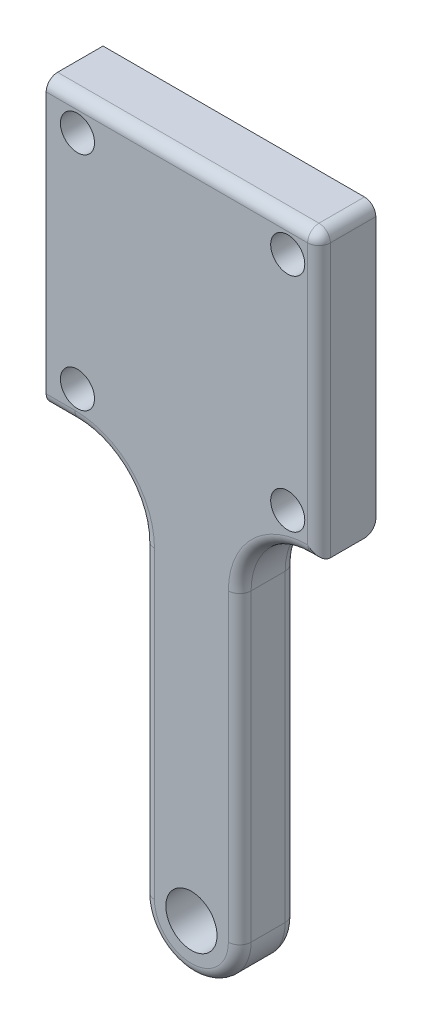
SolidWorks part; units mm, degrees
ref_plane "Alzado" through (0, 0, 0) normal (0, 0, 1) x (1, 0, 0)
ref_plane "Planta" through (0, 0, 0) normal (0, 1, 0) x (1, 0, 0)
ref_plane "Vista lateral" through (0, 0, 0) normal (1, 0, 0) x (0, 0, -1)
sketch "Croquis1" plane through (0, 0, 0) normal (0, 0, 1) x (1, 0, 0)
  line L0 (-2.2, 41.0126) -> (21, 41.0126) construction
  line L1 (21.9, 40.0126) -> (21.9, -1.4874) construction
  line L2 (-2.1, -1.4874) -> (-2.1, 41.0126) construction
  line L3 (-2.1, 41.0126) -> (21.9, 41.0126)
  line L4 (21.9, 41.0126) -> (21.9, 16.0126)
  line L5 (-2.1, 16.0126) -> (-2.1, 41.0126)
  line L6 (-2.1, 16.0126) -> (0.4278, 16.0126)
  line L7 (21, 16.0126) -> (-2.2, 16.0126) construction
  line L8 (21, 16.0126) -> (-2.2, 16.0126) construction
  line L9 (6.4278, -16.7515) -> (6.4278, 10.0126)
  line L10 (14.9278, -16.7515) -> (14.9278, 10.0126)
  line L11 (20.9278, 16.0126) -> (21.9, 16.0126)
  circle A0 centre (10.6778, -16.7515) radius 2.25 construction
  circle A1 centre (10.6778, -16.7515) radius 2.25
  circle A2 centre (10.6778, -16.7515) radius 4.25 construction
  arc A3 (6.4278, -16.7515) -> (14.9278, -16.7515) centre (10.6778, -16.7515) ccw
  arc A4 (0.4278, 16.0126) -> (6.4278, 10.0126) centre (0.4278, 10.0126) cw
  arc A5 (14.9278, 10.0126) -> (20.9278, 16.0126) centre (20.9278, 10.0126) cw
  circle A6 centre (0.65, 38.2626) radius 1.5 construction
  circle A7 centre (19.15, 38.2626) radius 1.5 construction
  circle A8 centre (19.15, 18.7626) radius 1.5 construction
  circle A9 centre (0.65, 18.7626) radius 1.5 construction
  circle A10 centre (0.65, 38.2626) radius 1.5
  circle A11 centre (19.15, 38.2626) radius 1.5
  circle A12 centre (19.15, 18.7626) radius 1.5
  circle A13 centre (0.65, 18.7626) radius 1.5
  point P23 (6.4278, 16.0126)
  point P26 (14.9278, 16.0126)
  dimension "D2" = 2
  dimension "D1" = 4.25
  dimension "D3" = 6
extrude "Saliente-Extruir1" add sketch "Croquis1" along normal blind 5
fillet "Redondeo1" radius 1 16 edges at (-0.8361, 16.0126, 0) (21.4139, 16.0126, 0) (16.6851, 14.2553, 0) (14.9278, -3.3694, 0) (10.6778, -21.0015, 0) (6.4278, -3.3694, 0) (-0.8361, 16.0126, 5) (4.6704, 14.2553, 5) (16.6851, 14.2553, 5) (14.9278, -3.3694, 5) (10.6778, -21.0015, 5) (4.6704, 14.2553, 0) (21.9, 41.0126, 2.5) (9.9, 41.0126, 5) (21.9, 28.5126, 5) (6.4278, -3.3694, 5)
